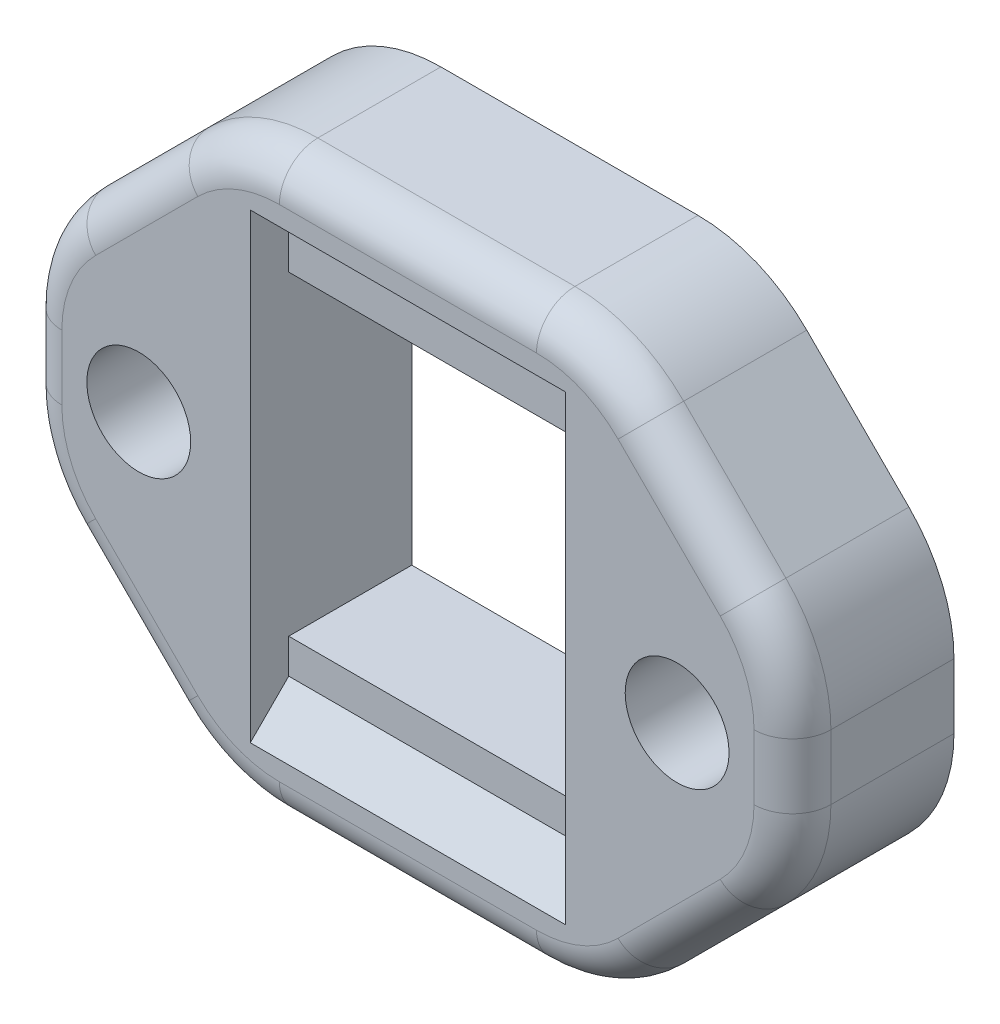
SolidWorks part; units mm, degrees
ref_plane "Front Plane" through (0, 0, 0) normal (0, 0, 1) x (1, 0, 0)
ref_plane "Top Plane" through (0, 0, 0) normal (0, 1, 0) x (1, 0, 0)
ref_plane "Right Plane" through (0, 0, 0) normal (1, 0, 0) x (0, 0, -1)
sketch "Sketch1" plane through (0, 0, 0) normal (0, 0, 1) x (1, 0, 0)
  line L1 (0, 5.1421) -> (20, 5.1421)
  line L2 (0, 5.1421) -> (0, 20.1421)
  line L3 (0, 20.1421) -> (20, 20.1421)
  line L4 (20, 5.1421) -> (20, 20.1421)
  dimension "D1" = 20
  dimension "D2" = 15
extrude "Boss-Extrude1" add sketch "Sketch1" along normal blind 4.2
sketch "Sketch2" plane through (0, 0, 4.2) normal (0, 0, 1) x (1, 0, 0)
  line L0 (0, 12.6421) -> (20, 12.6421) construction
  line L1 (5.9, 17.6421) -> (14.1, 17.6421)
  line L2 (5.9, 17.6421) -> (5.9, 7.6421)
  line L3 (5.9, 7.6421) -> (14.1, 7.6421)
  line L4 (14.1, 17.6421) -> (14.1, 7.6421)
  line L5 (0, 5.1421) -> (20, 5.1421) construction
  line L6 (10, 20.1421) -> (10, 5.1421) construction
  line L7 (20, 20.1421) -> (0, 20.1421) construction
  line L9 (0, 20.1421) -> (0, 5.1421) construction
  line L10 (20, 5.1421) -> (20, 20.1421) construction
  dimension "D1" = 8.2
  dimension "D2" = 10
  dimension "D4" = 5
  dimension "D5" = 4.1
extrude "Cut-Extrude1" cut sketch "Sketch2" against normal blind 1
sketch "Sketch3" plane through (0, 0, 3.2) normal (0, 0, 1) x (1, 0, 0)
  line L0 (5.9, 17.6421) -> (5.9, 7.6421) construction
  line L1 (5.9, 16.7421) -> (14.1, 16.7421)
  line L2 (5.9, 16.7421) -> (5.9, 8.5421)
  line L3 (5.9, 8.5421) -> (14.1, 8.5421)
  line L4 (14.1, 16.7421) -> (14.1, 8.5421)
  line L5 (14.1, 7.6421) -> (14.1, 17.6421) construction
  line L6 (14.1, 17.6421) -> (5.9, 17.6421) construction
  line L7 (5.9, 7.6421) -> (14.1, 7.6421) construction
  dimension "D1" = 0.9
  dimension "D2" = 0.9
extrude "Cut-Extrude2" cut sketch "Sketch3" against normal through all
chamfer "Chamfer1" distance 1 angle 45 2 edges at (10, 7.6421, 4.2) (10, 17.6421, 4.2)
sketch "Sketch4" plane through (0, 0, 4.2) normal (0, 0, 1) x (1, 0, 0)
  line L0 (10, 20.1421) -> (10, 5.1421) construction
  line L1 (20, 20.1421) -> (0, 20.1421) construction
  line L2 (0, 5.1421) -> (20, 5.1421) construction
  line L3 (0, 12.6421) -> (20, 12.6421) construction
  line L4 (0, 20.1421) -> (0, 5.1421) construction
  line L5 (20, 5.1421) -> (20, 20.1421) construction
  circle A0 centre (3, 12.6421) radius 1.35
  circle A1 centre (17, 12.6421) radius 1.35
  dimension "D1" = 2.7
  dimension "D2" = 7
extrude "Cut-Extrude3" cut sketch "Sketch4" against normal through all
chamfer "Chamfer2" distance 5 angle 45 4 edges at (0, 20.1421, 2.1) (0, 5.1421, 2.1) (20, 5.1421, 2.1) (20, 20.1421, 2.1)
fillet "Fillet1" radius 4 8 edges at (0, 15.1421, 2.1) (5, 20.1421, 2.1) (15, 20.1421, 2.1) (20, 15.1421, 2.1) (20, 10.1421, 2.1) (15, 5.1421, 2.1) (5, 5.1421, 2.1) (0, 10.1421, 2.1)
fillet "Fillet2" radius 1 16 edges at (5.1261, 19.8377, 4.2) (10, 20.1421, 4.2) (14.8739, 19.8377, 4.2) (17.5, 17.6421, 4.2) (19.6955, 15.016, 4.2) (20, 12.6421, 4.2) (19.6955, 10.2683, 4.2) (17.5, 7.6421, 4.2) (14.8739, 5.4466, 4.2) (10, 5.1421, 4.2) (5.1261, 5.4466, 4.2) (2.5, 7.6421, 4.2) (0.3045, 10.2683, 4.2) (0, 12.6421, 4.2) (0.3045, 15.016, 4.2) (2.5, 17.6421, 4.2)
